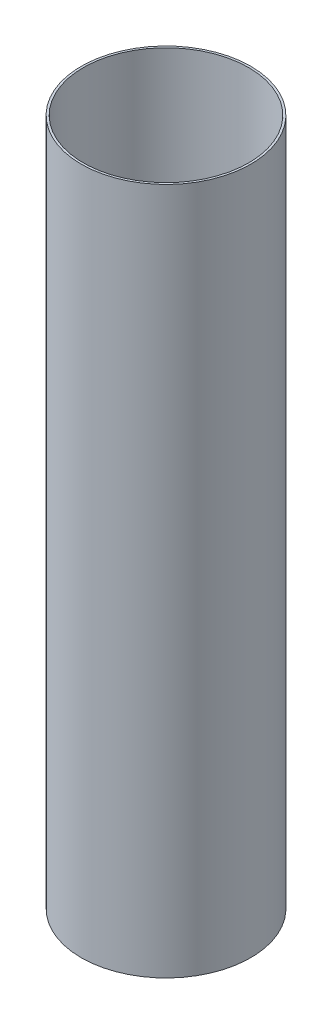
SolidWorks part; units mm, degrees
material "C-Glass Fiber"
ref_plane "Front Plane" through (0, 0, 0) normal (0, 0, 1) x (1, 0, 0)
ref_plane "Top Plane" through (0, 0, 0) normal (0, 1, 0) x (1, 0, 0)
ref_plane "Right Plane" through (0, 0, 0) normal (1, 0, 0) x (0, 0, -1)
sketch "Sketch2" plane through (0, 0, 0) normal (0, 1, 0) x (1, 0, 0)
  circle A0 centre (0, 0) radius 76.3651
  circle A1 centre (0, 0) radius 78.359
  dimension "D1" = 152.7302
  dimension "D2" = 156.718
extrude "Boss-Extrude1" add sketch "Sketch2" along normal blind 635
